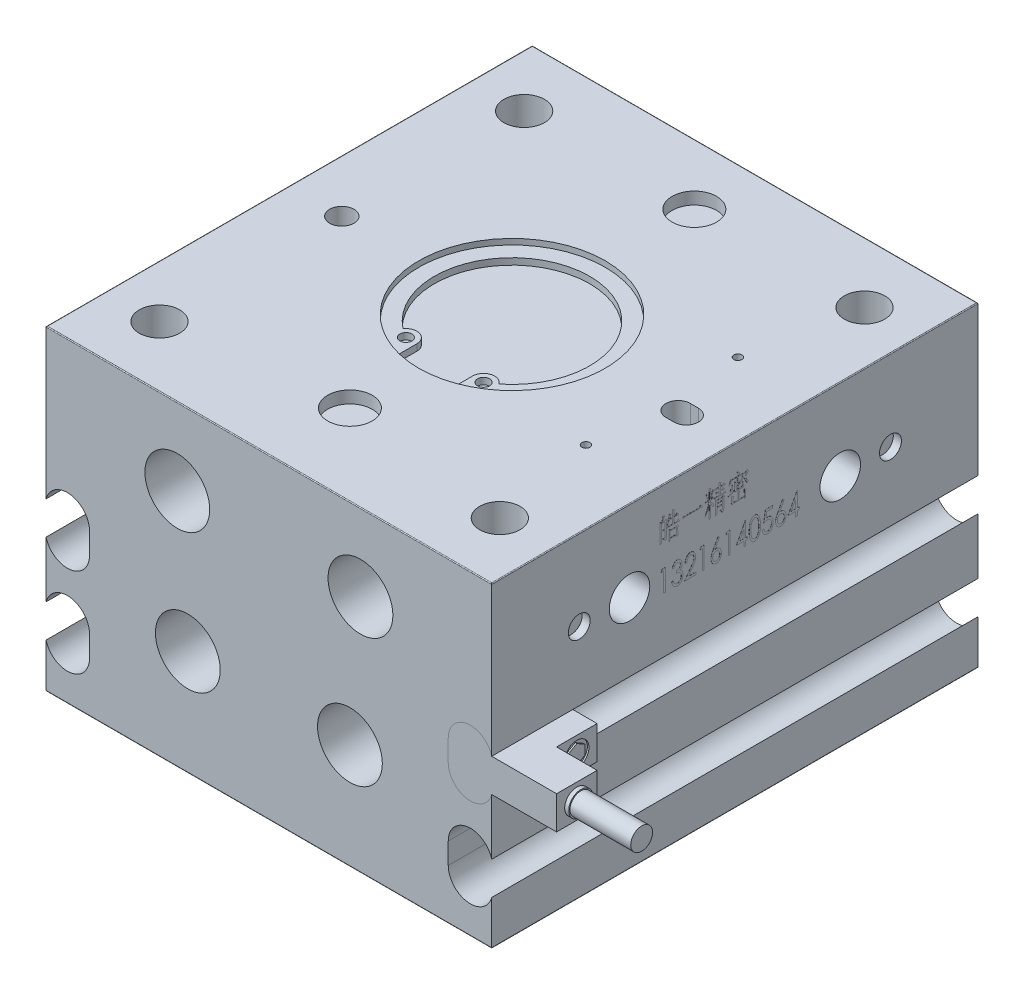
SolidWorks part; units mm, degrees
ref_plane "前视基准面" through (0, 0, 0) normal (0, 0, 1) x (1, 0, 0)
ref_plane "上视基准面" through (0, 0, 0) normal (0, 1, 0) x (1, 0, 0)
ref_plane "右视基准面" through (0, 0, 0) normal (1, 0, 0) x (0, 0, -1)
sketch "草图1" plane through (0, 0, 0) normal (0, 1, 0) x (1, 0, 0)
  line L0 (0, 0) -> (0, 60) construction
  line L1 (-27.5, 0) -> (27.5, 0)
  line L2 (-27.5, 0) -> (-27.5, 60)
  line L3 (-27.5, 60) -> (27.5, 60)
  line L4 (27.5, 0) -> (27.5, 60)
  line L5 (21.5, 30) -> (20.5, 30) construction
  line L6 (21, 7.5) -> (-21, 7.5)
  line L7 (21, 7.5) -> (21, 52.5)
  line L8 (21, 52.5) -> (-21, 52.5)
  line L9 (-21, 7.5) -> (-21, 52.5)
  line L10 (21, 7.5) -> (-21, 52.5) construction
  line L11 (21, 52.5) -> (-21, 7.5) construction
  line L12 (21.5, 28.5) -> (20.5, 28.5)
  line L13 (21.5, 31.5) -> (20.5, 31.5)
  line L14 (0, 30) -> (-21, 30) construction
  line L15 (-4.7917, 21.7006) -> (0, 30) construction
  line L16 (-3.4417, 21.7006) -> (-3.4417, 19.0271)
  line L17 (3.4417, 21.7006) -> (3.4417, 19.0271)
  circle A0 centre (-21, 30) radius 1.5
  circle A1 centre (-21, 7.5) radius 2.5
  arc A2 (21.5, 28.5) -> (21.5, 31.5) centre (21.5, 30) ccw
  arc A3 (20.5, 31.5) -> (20.5, 28.5) centre (20.5, 30) ccw
  circle A4 centre (0, 10) radius 2.75
  circle A5 centre (0, 30) radius 11.5
  circle A6 centre (0, 30) radius 0.75
  circle A7 centre (0, 30) radius 9.5833
  circle A8 centre (-4.7917, 21.7006) radius 0.75
  circle A9 centre (-4.7917, 21.7006) radius 1.35
  circle A10 centre (4.7917, 21.7006) radius 0.75
  circle A11 centre (4.7917, 21.7006) radius 1.35
  circle A12 centre (18.5, 20.625) radius 0.5
  circle A13 centre (18.5, 39.375) radius 0.5
  point P0 (0, 0)
  point P8 (0, 30)
  point P15 (-21, 33)
  point P17 (-11, 7.5)
  point P20 (21, 30)
  point P25 (19, 30)
  point P26 (23, 30)
  dimension "D1" = 19.1667
  dimension "K2" = 3
  dimension "K3" = 5
  dimension "K5" = 5.5
  dimension "K6" = 23
  dimension "深3" = 1.5
  dimension "D4" = 1.5
  dimension "D5" = 2.7
  dimension "D7" = 1
  dimension "C" = 60
  dimension "K1" = 55
  dimension "B" = 45
  dimension "D2" = 3
  dimension "深" = 3
  dimension "深2" = 10
  dimension "K4" = 4
  dimension "A" = 40
  dimension "D3" = 30
  dimension "D6" = 0.5
  dimension "D8" = 18.75
  dimension "K7" = 42
sketch "草图2" plane through (0, 0, 0) normal (0, 0, 1) x (1, 0, 0)
  line L0 (-27.5, 38.5) -> (27.5, 38.5) construction
  line L1 (-27.5, 0) -> (27.5, 0)
  line L2 (-27.5, 0) -> (-27.5, 39)
  line L3 (-27.5, 39) -> (27.5, 39)
  line L4 (27.5, 0) -> (27.5, 39)
  line L5 (0, 0) -> (0, 39) construction
  line L6 (-21.5, 38.5) -> (-21.5, -19) construction
  line L7 (-21.5, -19) -> (21.5, -19) construction
  line L8 (21.5, -19) -> (21.5, 38.5) construction
  line L9 (21.5, 18.5) -> (27.5, 18.5) construction
  line L10 (-11.3, 35.2735) -> (-16.3, 32.3868)
  line L11 (-16.3, 32.3868) -> (-16.3, 26.6132)
  line L12 (-16.3, 26.6132) -> (-11.3, 23.7265)
  line L13 (-11.3, 23.7265) -> (-6.3, 26.6132)
  line L14 (-6.3, 26.6132) -> (-6.3, 32.3868)
  line L15 (-6.3, 32.3868) -> (-11.3, 35.2735)
  line L16 (21.5, 7.5) -> (27.5, 7.5) construction
  line L17 (24.8662, 17.1905) -> (24.8662, 19.8095) construction
  line L18 (22.1324, 17.1905) -> (22.1324, 19.8095)
  line L19 (27.6, 17.1905) -> (27.6, 19.8095)
  line L20 (21.5, 13) -> (27.5, 13) construction
  line L21 (24.8662, 8.8095) -> (24.8662, 6.1905) construction
  line L22 (22.1324, 8.8095) -> (22.1324, 6.1905)
  line L23 (27.6, 8.8095) -> (27.6, 6.1905)
  circle A0 centre (-11.3, 29.5) radius 4
  circle A1 centre (11.3, 29.5) radius 4
  circle A2 centre (-10, 13) radius 4
  circle A3 centre (10, 13) radius 4
  circle A4 centre (-11.3, 29.5) radius 5 construction
  circle A5 centre (-17.5, -11) radius 2.5
  circle A6 centre (17.5, -11) radius 2.5
  arc A7 (22.1324, 17.1905) -> (27.6, 17.1905) centre (24.8662, 17.1905) ccw
  arc A8 (27.6, 19.8095) -> (22.1324, 19.8095) centre (24.8662, 19.8095) ccw
  arc A9 (22.1324, 8.8095) -> (27.6, 8.8095) centre (24.8662, 8.8095) cw
  arc A10 (27.6, 6.1905) -> (22.1324, 6.1905) centre (24.8662, 6.1905) cw
  circle A11 centre (-11.3, 29.5) radius 7.5
  circle A12 centre (-11.3, 29.5) radius 3
  point P38 (24.5, 18.5)
  point P41 (24.8662, 18.5)
  point P50 (24.8662, 7.5)
  dimension "D1" = 0.1
  dimension "L5" = 8
  dimension "L10" = 10
  dimension "L13" = 5
  dimension "L16" = 15
  dimension "L17" = 6
  dimension "L18" = 8
  dimension "L1" = 39
  dimension "L2" = 0.5
  dimension "L3" = 9
  dimension "L4" = 22.6
  dimension "L6" = 16.5
  dimension "L7" = 20
  dimension "L8" = 43
  dimension "L9" = 19
  dimension "L11" = 8
  dimension "L12" = 35
  dimension "L14" = 20.5
  dimension "L15" = 11
  dimension "D2" = 1.2647
  dimension "D3" = 2.619
sketch "草图3" plane through (0, 0, 0) normal (1, 0, 0) x (0, 0, -1)
  line L0 (0, 0) -> (0, 39) construction
  line L1 (0, 39) -> (30, 39)
  line L2 (0, 39) -> (0, 0)
  line L3 (0, 0) -> (60, 0)
  line L4 (60, 39) -> (60, 0)
  line L5 (0, 0) -> (60, 0) construction
  line L6 (-34, 19.5) -> (94, 19.5) construction
  line L7 (30, 39) -> (60, 39)
  line L8 (30, 39) -> (30, 0) construction
  line L9 (-17, 38.5) -> (-4, 38.5)
  line L10 (-4, 38.5) -> (-4, -19)
  line L11 (-4, -19) -> (-13, -19)
  line L12 (-13, -19) -> (-13, 0)
  line L13 (-13, 0) -> (-17, 0)
  line L14 (-17, 0) -> (-17, 38.5)
  line L15 (-17, 29.5) -> (0, 29.5) construction
  line L16 (0, 13) -> (30, 13) construction
  line L17 (15, 13) -> (15, 0) construction
  line L18 (5, 13) -> (5, 21)
  line L19 (5, 21) -> (25, 21)
  line L20 (25, 21) -> (25, 13)
  line L21 (30, 0) -> (30, -15) construction
  line L22 (16, 29) -> (23, 29) construction
  circle A0 centre (-17, 29.5) radius 3
  circle A1 centre (17, 29) radius 2.5
  circle A2 centre (43, 29) radius 2.5
  circle A3 centre (10.8, 29) radius 1.35
  circle A4 centre (49.2, 29) radius 1.35
  circle A5 centre (16, 29) radius 2.5
  point P12 (-4, 19.5)
  point P14 (-15, 19.5)
  point P21 (-19, 19.5)
  point P24 (-10.5, 38.5)
  dimension "D2" = 2.7
  dimension "M5" = 6
  dimension "接管口径" = 5
  dimension "M7" = 5
  dimension "D1" = 2
  dimension "E" = 68
  dimension "G" = 128
  dimension "F" = 98
  dimension "M1" = 9
  dimension "M2" = 13
  dimension "M3" = 19
  dimension "M4" = 6.5
  dimension "D3" = 5.2
  dimension "H" = 26
  dimension "M6" = 10
  dimension "D4" = 20
  dimension "行程" = 15
  dimension "D" = 28
  dimension "M8" = 7
  dimension "缸径" = 16
  dimension "M9" = 10
sketch "草图4" plane through (0, 0, 0) normal (0, 0, 1) x (1, 0, 0)
  line L0 (-27.5, 39) -> (27.5, 39) construction
  line L1 (-27.5, 0) -> (-27.5, 39) construction
  line L2 (27.5, 0) -> (27.5, 39) construction
  line L3 (-27.5, 0) -> (27.5, 0) construction
  line L4 (-27.5, 39) -> (27.5, 39)
  line L5 (-27.5, 0) -> (-27.5, 5.4578)
  line L6 (27.5, 0) -> (27.5, 5.4578)
  line L7 (-27.5, 0) -> (27.5, 0)
  line L8 (22.1324, 17.1905) -> (22.1324, 19.8095) construction
  line L9 (22.1324, 8.8095) -> (22.1324, 6.1905) construction
  line L10 (27.6, 8.8095) -> (27.6, 6.1905) construction
  line L11 (27.6, 17.1905) -> (27.6, 19.8095) construction
  line L12 (22.1324, 17.1905) -> (22.1324, 19.8095)
  line L13 (22.1324, 8.8095) -> (22.1324, 6.1905)
  line L14 (27.6, 8.8095) -> (27.6, 6.1905)
  line L15 (27.6, 17.1905) -> (27.6, 19.8095)
  line L16 (27.5, 20.5422) -> (27.5, 39)
  line L17 (27.5, 9.5422) -> (27.5, 16.4578)
  line L18 (0, 39) -> (0, 0) construction
  line L19 (-27.6, 17.1905) -> (-27.6, 19.8095)
  line L20 (-27.6, 8.8095) -> (-27.6, 6.1905)
  line L21 (-22.1324, 8.8095) -> (-22.1324, 6.1905)
  line L22 (-22.1324, 17.1905) -> (-22.1324, 19.8095)
  line L23 (-27.5, 20.5422) -> (-27.5, 39)
  line L24 (-27.5, 9.5422) -> (-27.5, 16.4578)
  arc A4 (27.6, 19.8095) -> (22.1324, 19.8095) centre (24.8662, 19.8095) ccw construction
  arc A5 (27.6, 8.8095) -> (22.1324, 8.8095) centre (24.8662, 8.8095) ccw construction
  arc A10 (27.6, 19.8095) -> (22.1324, 19.8095) centre (24.8662, 19.8095) ccw
  arc A11 (27.6, 8.8095) -> (22.1324, 8.8095) centre (24.8662, 8.8095) ccw
  arc A12 (22.1324, 17.1905) -> (27.6, 17.1905) centre (24.8662, 17.1905) ccw construction
  arc A13 (22.1324, 6.1905) -> (27.6, 6.1905) centre (24.8662, 6.1905) ccw construction
  arc A14 (22.1324, 17.1905) -> (27.6, 17.1905) centre (24.8662, 17.1905) ccw
  arc A15 (22.1324, 6.1905) -> (27.6, 6.1905) centre (24.8662, 6.1905) ccw
  arc A16 (-22.1324, 6.1905) -> (-27.6, 6.1905) centre (-24.8662, 6.1905) cw
  arc A17 (-22.1324, 17.1905) -> (-27.6, 17.1905) centre (-24.8662, 17.1905) cw
  arc A18 (-27.6, 8.8095) -> (-22.1324, 8.8095) centre (-24.8662, 8.8095) cw
  arc A19 (-27.6, 19.8095) -> (-22.1324, 19.8095) centre (-24.8662, 19.8095) cw
extrude "凸台-拉伸1" add sketch "草图4" against normal up to vertex (60 mm away) contours A15 L13 A11 L17 A14 L12 A10 L16 L4 L5 L7 L6 | L18 L4 L23 A19 L22 A17 L24 A18 L21 A16 L5 L7 region at (-12.9176, 19.9879, 0) region at (12.9176, 19.9879, 0) up to point (0, 39, -60)
sketch "草图5" plane through (0, 39, 0) normal (0, 1, 0) x (1, 0, 0)
  circle A0 centre (0, 30) radius 11.5 construction
  circle A1 centre (0, 30) radius 11.5
extrude "切除-拉伸1" cut sketch "草图5" against normal blind 1.5
sketch "草图6" plane through (0, 37.5, 0) normal (0, 1, 0) x (1, 0, 0)
  line L1 (-3.4417, 21.7006) -> (-3.4417, 19.0271) construction
  line L2 (3.4417, 21.7006) -> (3.4417, 19.0271) construction
  line L4 (-3.4417, 21.7006) -> (-3.4417, 19.0271)
  line L5 (3.4417, 21.7006) -> (3.4417, 19.0271)
  arc A0 (5.9104, 22.4563) -> (-5.9104, 22.4563) centre (0, 30) ccw
  circle A1 centre (0, 30) radius 9.5833 construction
  circle A4 centre (0, 30) radius 11.5 construction
  circle A5 centre (-4.7917, 21.7006) radius 1.35 construction
  circle A6 centre (-4.7917, 21.7006) radius 0.75 construction
  circle A10 centre (4.7917, 21.7006) radius 1.35 construction
  circle A11 centre (4.7917, 21.7006) radius 0.75 construction
  circle A12 centre (0, 30) radius 11.5
  arc A13 (-3.4417, 21.7006) -> (-5.9104, 22.4563) centre (-4.7917, 21.7006) ccw
  circle A14 centre (-4.7917, 21.7006) radius 0.75
  arc A16 (5.9104, 22.4563) -> (3.4417, 21.7006) centre (4.7917, 21.7006) ccw
  circle A17 centre (4.7917, 21.7006) radius 0.75
  circle M1 centre (0, 30) radius 11.5
extrude "凸台-拉伸2" add sketch "草图6" along normal blind 0.8 contours A0 A16 L5 L4 A13 A17 A14 M1 region at (-3.7632, 37.5, -20.3638)
sketch "草图7" plane through (0, 39, 0) normal (0, 1, 0) x (1, 0, 0)
  line L0 (21.5, 31.5) -> (20.5, 31.5) construction
  line L1 (21.5, 28.5) -> (20.5, 28.5) construction
  line L2 (21.5, 31.5) -> (20.5, 31.5)
  line L3 (21.5, 28.5) -> (20.5, 28.5)
  circle A0 centre (-21, 30) radius 1.5 construction
  circle A1 centre (-21, 30) radius 1.5
  arc A2 (20.5, 31.5) -> (20.5, 28.5) centre (20.5, 30) ccw construction
  arc A3 (20.5, 31.5) -> (20.5, 28.5) centre (20.5, 30) ccw
  arc A4 (21.5, 28.5) -> (21.5, 31.5) centre (21.5, 30) ccw construction
  arc A5 (21.5, 28.5) -> (21.5, 31.5) centre (21.5, 30) ccw
  circle A6 centre (18.5, 20.625) radius 0.5 construction
  circle A7 centre (18.5, 39.375) radius 0.5 construction
  circle A8 centre (18.5, 20.625) radius 0.5
  circle A9 centre (18.5, 39.375) radius 0.5
extrude "切除-拉伸2" cut sketch "草图7" against normal blind 3
sketch "草图8" plane through (0, 39, 0) normal (0, 1, 0) x (1, 0, 0)
  line L0 (21, 52.5) -> (-21, 52.5) construction
  circle A0 centre (0, 10) radius 2.75 construction
  circle A1 centre (0, 10) radius 2.75
  circle A2 centre (0, 52.5) radius 2.75
extrude "1025" cut sketch "草图8" against normal blind 1.5
sketch "草图9" plane through (0, 39, 0) normal (0, 1, 0) x (1, 0, 0)
  circle A0 centre (-21, 7.5) radius 2.5 construction
  circle A1 centre (-21, 7.5) radius 2.5
  circle A2 centre (-21, 52.5) radius 2.5
  circle A3 centre (21, 52.5) radius 2.5
  circle A4 centre (21, 7.5) radius 2.5
extrude "切除-拉伸4" cut sketch "草图9" against normal blind 10
cosmetic thread "装饰螺纹线1" parameters "D2"=5.625
cosmetic thread "装饰螺纹线2" parameters "D2"=5.625
cosmetic thread "装饰螺纹线3" parameters "D2"=5.625
cosmetic thread "装饰螺纹线4" parameters "D2"=5.625
sketch "草图10" plane through (-27.5, 0, 0) normal (-1, 0, 0) x (0, 0, 1)
  line L0 (-30, 0) -> (-30, -15) construction
  line L1 (-30, 0) -> (-30, -15) construction
  circle A0 centre (-16, 29) radius 2.5 construction
  circle A1 centre (-16, 29) radius 2.5
  circle A2 centre (-44, 29) radius 2.5
extrude "切除-拉伸5" cut sketch "草图10" against normal blind 7
sketch "草图12" plane through (0, 0, 0) normal (0, 0, 1) x (1, 0, 0)
  circle A0 centre (11.3, 29.5) radius 4 construction
  circle A1 centre (10, 13) radius 4
  circle A2 centre (10, 13) radius 4 construction
  circle A3 centre (-10, 13) radius 4 construction
  circle A4 centre (-11.3, 29.5) radius 4 construction
  circle A5 centre (11.3, 29.5) radius 4
  circle A6 centre (-10, 13) radius 4
  circle A7 centre (-11.3, 29.5) radius 4
extrude "切除-拉伸6" cut sketch "草图12" against normal up to vertex (25 mm away) up to point (0, 21, -25)
ref_plane "基准面1" through (0, 0, -30) normal (0, 0, -1) x (-1, 0, 0)
mirror "镜向1" about plane through (0, 0, -30) normal (0, 0, -1) of "切除-拉伸6"
sketch "草图15" plane through (27.5, 0, 0) normal (1, 0, 0) x (0, 0, -1)
  circle A0 centre (17, 29) radius 2.5 construction
  circle A1 centre (43, 29) radius 2.5 construction
  circle A2 centre (17, 29) radius 2.5
  circle A3 centre (43, 29) radius 2.5
extrude "切除-拉伸8" cut sketch "草图15" against normal blind 6
cosmetic thread "装饰螺纹线5" parameters "D2"=6
cosmetic thread "装饰螺纹线6" parameters "D2"=6
fillet "圆角1" radius 0.1 8 edges at (0, 0, -60) (-27.5, 0, -30) (0, 0, 0) (27.5, 0, -30) (0, 39, -60) (27.5, 39, -30) (0, 39, 0) (-27.5, 39, -30)
sketch "草图23" plane through (27.5, -1.0441, 62.1617) normal (1, 0, 0) x (0, 0, -1)
  line L0 (82.6617, 39.9441) -> (82.6617, 33.8249) construction
  line L1 (122.1617, 39.9441) -> (62.1617, 39.9441) construction
  line L2 (82.6617, 33.8249) -> (82.6617, 27.7056) construction
  line L3 (82.6617, 27.7056) -> (82.6617, 21.5863) construction
  line L4 (82.6617, 33.8249) -> (81.6617, 33.8249) construction
  line L5 (122.1617, 21.5863) -> (62.1617, 21.5863) construction
  line L9 (82.6617, 33.8249) -> (83.6617, 33.8249) construction
  circle A0 centre (79.1617, 30.0441) radius 2.5 construction
  circle A1 centre (105.1617, 30.0441) radius 2.5 construction
  circle A2 centre (79.1617, 30.0441) radius 2.5 construction
  circle A3 centre (105.1617, 30.0441) radius 2.5 construction
  text T0 "皓一精密\r\n13216140564" font "Century Gothic" height in points 10
  point P4 (82.6617, 30.7652)
  point P15 (81.6617, 30.0441)
  dimension "D1" = 1
extrude "凸台-拉伸7" add sketch "草图23" along normal blind 0.01
sketch "草图16" plane through (0, 0, 0) normal (1, 0, 0) x (0, 0, -1)
  line L0 (-4, 19.5) -> (-19, 19.5)
  dimension "D1" = 15
sketch "草图17" plane through (27.5, 0, 0) normal (1, 0, 0) x (0, 0, -1)
  circle A0 centre (10.8, 29) radius 1.35 construction
  circle A1 centre (49.2, 29) radius 1.35 construction
  circle A2 centre (10.8, 29) radius 1.35
  circle A3 centre (49.2, 29) radius 1.35
extrude "切除-拉伸9" cut sketch "草图17" against normal blind 1
sketch "草图18" plane through (0, 0, 0) normal (0, 0, 1) x (1, 0, 0)
  line L0 (22.1324, 17.1905) -> (22.1324, 19.8095) construction
  line L1 (22.1324, 17.1905) -> (22.1324, 19.8095)
  line L2 (27.5, 20.5422) -> (30.5, 20.5422)
  line L3 (30.5, 20.5422) -> (30.5, 16.4578)
  line L4 (30.5, 16.4578) -> (27.5, 16.4578)
  arc A0 (27.5, 20.5422) -> (22.1324, 19.8095) centre (24.8662, 19.8095) ccw construction
  arc A1 (22.1324, 17.1905) -> (27.5, 16.4578) centre (24.8662, 17.1905) ccw construction
  arc A2 (27.5, 20.5422) -> (22.1324, 19.8095) centre (24.8662, 19.8095) ccw
  arc A3 (22.1324, 17.1905) -> (27.5, 16.4578) centre (24.8662, 17.1905) ccw
  dimension "D1" = 3
extrude "凸台-拉伸3" add sketch "草图18" against normal blind 10 separate body
sketch "草图19" plane through (30.5, 0, 0) normal (1, 0, 0) x (0, 0, -1)
  line L0 (5, 20.5422) -> (5, 16.4578) construction
  line L1 (10, 20.5422) -> (0, 20.5422) construction
  line L2 (10, 16.4578) -> (0, 16.4578) construction
  line L3 (5, 18.5) -> (10, 18.5) construction
  line L4 (10, 16.4578) -> (10, 20.5422) construction
  line L10 (7.5, 19.6547) -> (6.5, 19.0774)
  line L11 (6.5, 19.0774) -> (6.5, 17.9226)
  line L12 (6.5, 17.9226) -> (7.5, 17.3453)
  line L13 (-10, 30.5422) -> (-10, 6.4578)
  line L14 (-10, 6.4578) -> (20, 6.4578)
  line L15 (20, 6.4578) -> (20, 30.5422)
  line L16 (20, 30.5422) -> (-10, 30.5422)
  line L17 (-10, 30.5422) -> (-10, 6.4578)
  line L18 (-10, 6.4578) -> (20, 6.4578)
  line L19 (7.5, 17.3453) -> (8.5, 17.9226)
  line L20 (20, 30.5422) -> (-10, 30.5422)
  line L21 (8.5, 17.9226) -> (8.5, 19.0774)
  line L22 (8.5, 19.0774) -> (7.5, 19.6547)
  circle A1 centre (7.5, 18.5) radius 1.5
  circle A2 centre (7.5, 18.5) radius 1 construction
  dimension "D1" = 10
  dimension "D3" = 2
  dimension "D2" = 3
extrude "切除-拉伸10" cut sketch "草图19" against normal blind 0.2 contours A1 L22 L21 L19 L12 L11 L10 region at (30.5, 18.5, -6.0424)
sketch "草图20" plane through (30.5, 0, 0) normal (1, 0, 0) x (0, 0, -1)
  line L0 (5, 20.5422) -> (5, 16.4578)
  line L1 (10, 20.5422) -> (0, 20.5422) construction
  line L4 (10, 16.4578) -> (10, 20.5422)
  line L5 (0, 20.5422) -> (0, 16.4578)
  line L7 (10, 20.5422) -> (0, 20.5422)
  line L8 (0, 20.5422) -> (0, 16.4578)
  line L10 (0, 16.4578) -> (10, 16.4578)
  line L11 (5, 20.5422) -> (0, 20.5422)
  line L12 (0, 16.4578) -> (5, 16.4578)
  dimension "D1" = 0
extrude "凸台-拉伸4" add sketch "草图20" along normal blind 5
sketch "草图21" plane through (35.5, 0, 0) normal (1, 0, 0) x (0, 0, -1)
  line L0 (0, 20.5422) -> (5, 16.4578) construction
  circle A0 centre (2.5, 18.5) radius 1.35
  dimension "D1" = 2.7
extrude "凸台-拉伸5" add sketch "草图21" along normal blind 8
sketch "草图22" plane through (35.5, 0, 0) normal (1, 0, 0) x (0, 0, -1)
  circle A0 centre (2.5, 18.5) radius 1.5
  dimension "D1" = 3
extrude "凸台-拉伸6" add sketch "草图22" along normal blind 0.5
mirror "镜向2" about plane through (0, 0, -30) normal (0, 0, -1) of bodies 120 118
delete or keep bodies "1" [suppressed] type delete bodies bodies 120
delete or keep bodies "2" type delete bodies bodies 119
